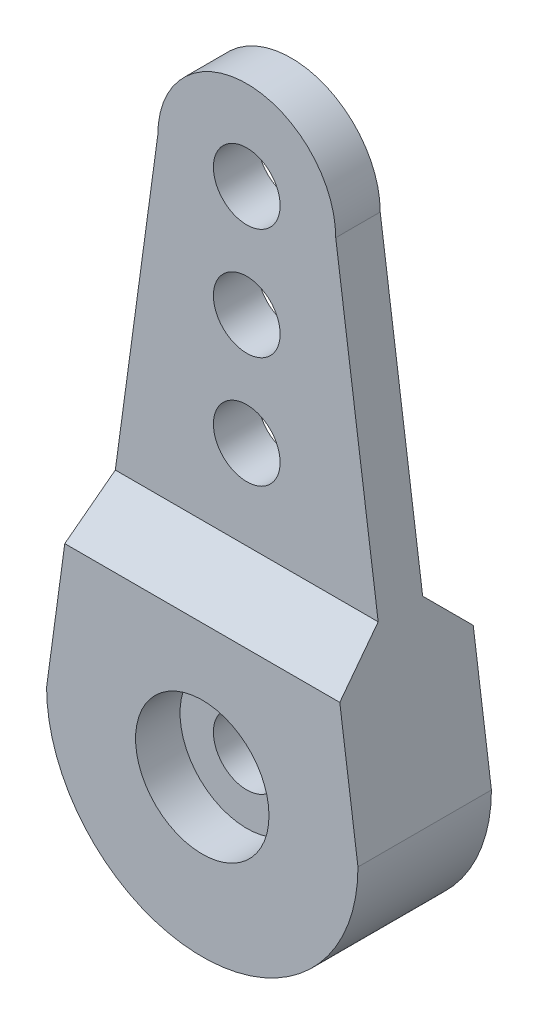
SolidWorks part; units mm, degrees
ref_plane "Front Plane" through (0, 0, 0) normal (0, 0, 1) x (1, 0, 0)
ref_plane "Top Plane" through (0, 0, 0) normal (0, 1, 0) x (1, 0, 0)
ref_plane "Right Plane" through (0, 0, 0) normal (1, 0, 0) x (0, 0, -1)
sketch "Sketch1" plane through (0, 0, 0) normal (0, 0, 1) x (1, 0, 0)
  line L0 (-7, 0) -> (-4, 22)
  line L1 (7, 0) -> (4, 22)
  arc A2 (4, 22) -> (-4, 22) centre (0, 22) ccw
  arc A3 (-7, 0) -> (7, 0) centre (0, 0) ccw
  dimension "D1" = 7
  dimension "D2" = 4
  dimension "D3" = 22
extrude "Boss-Extrude1" add sketch "Sketch1" along normal mid plane 2
sketch "Sketch2" plane through (0, 0, 0) normal (0, 0, 1) x (1, 0, 0)
  line L4 (0, -7) -> (8.7632, -7) construction
  line L5 (-5.9091, 8) -> (5.9091, 8)
  line L6 (7, 0) -> (4, 22) construction
  line L7 (-4, 22) -> (-7, 0) construction
  line L8 (7, 0) -> (5.9091, 8)
  line L9 (-5.9091, 8) -> (-7, 0)
  circle A2 centre (0, 0) radius 3
  arc A4 (-7, 0) -> (7, 0) centre (0, 0) ccw construction
  arc A5 (-7, 0) -> (7, 0) centre (0, 0) ccw
  dimension "D2" = 6
  dimension "D1" = 15
extrude "Boss-Extrude2" add sketch "Sketch2" along normal mid plane 6
chamfer "Chamfer1" distance 2 angle 45 2 edges at (0, 8, -3) (0, 8, 3)
sketch "Sketch3" plane through (0, 0, 1) normal (0, 0, 1) x (1, 0, 0)
  line L2 (0, 22) -> (0, 17) construction
  circle A3 centre (0, 22) radius 1.5
  circle A4 centre (0, 17) radius 1.5
  circle A5 centre (0, 12) radius 1.5
  point P14 (0, 0)
  dimension "D4" = 3
  dimension "D6" = 5
  dimension "D5" = 3
extrude "Cut-Extrude1" cut sketch "Sketch3" against normal through all
sketch "Sketch4" plane through (0, 0, 1) normal (0, 0, 1) x (1, 0, 0)
  circle A0 centre (0, 0) radius 1.5
  dimension "D1" = 3
extrude "Cut-Extrude2" cut sketch "Sketch4" against normal through all
